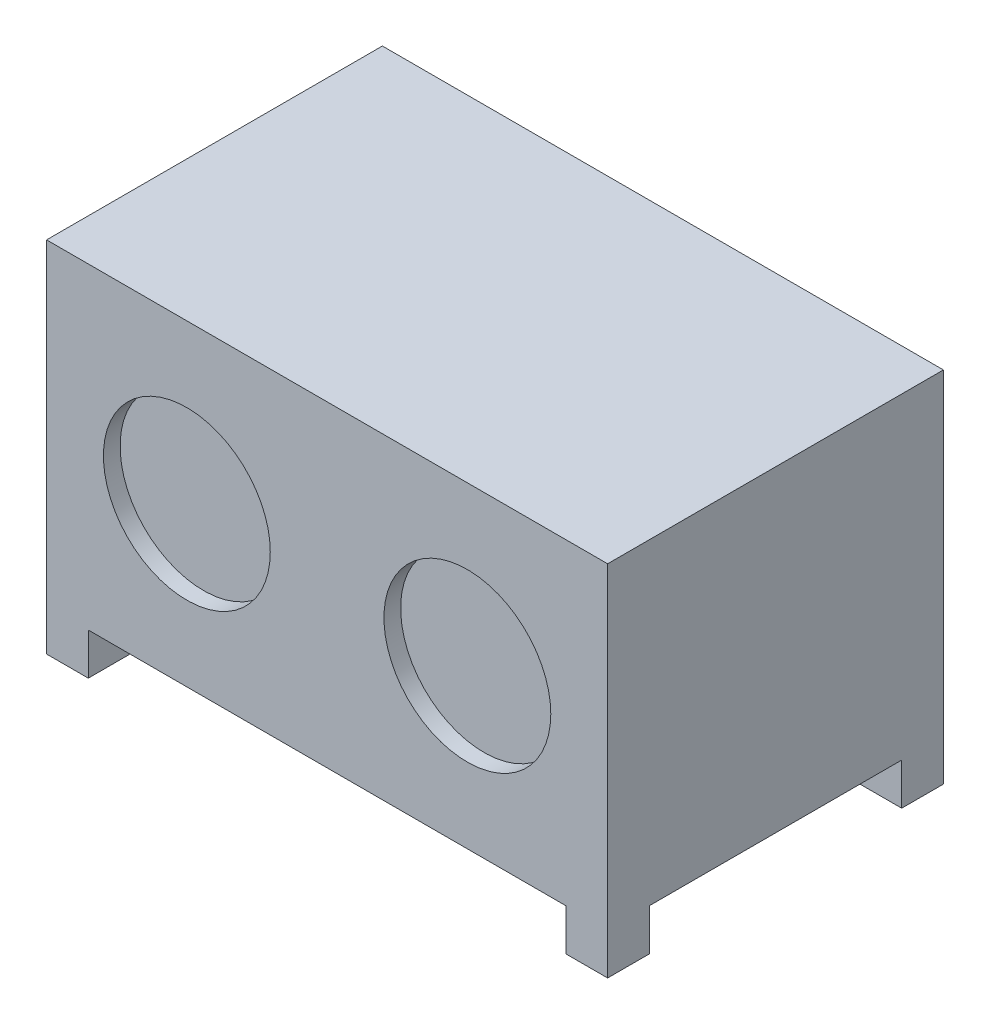
SolidWorks part; units mm, degrees
ref_plane "Front" through (0, 0, 0) normal (0, 0, 1) x (1, 0, 0)
ref_plane "Top" through (0, 0, 0) normal (0, 1, 0) x (1, 0, 0)
ref_plane "Right" through (0, 0, 0) normal (1, 0, 0) x (0, 0, -1)
sketch "Sketch1" plane through (0, 0, 0) normal (0, 1, 0) x (1, 0, 0)
  line L1 (-854.075, 511.175) -> (854.075, 511.175)
  line L2 (-854.075, 511.175) -> (-854.075, -511.175)
  line L3 (-854.075, -511.175) -> (854.075, -511.175)
  line L4 (854.075, 511.175) -> (854.075, -511.175)
  line L5 (-854.075, 511.175) -> (854.075, -511.175) construction
  line L6 (-854.075, -511.175) -> (854.075, 511.175) construction
  point P0 (0, 0)
  dimension "D1" = 1708.15
  dimension "D2" = 1022.35
extrude "Boss-Extrude1" add sketch "Sketch1" along normal blind 965.2
sketch "Sketch2" plane through (0, 0, 511.175) normal (0, 0, 1) x (1, 0, 0)
  line L0 (0, 0) -> (0, 965.2) construction
  line L1 (-854.075, 0) -> (854.075, 0) construction
  line L2 (-854.075, 965.2) -> (854.075, 965.2) construction
  line L3 (0, 482.6) -> (-854.075, 482.6) construction
  line L4 (-854.075, 965.2) -> (-854.075, 0) construction
  line L5 (0, 482.6) -> (854.075, 482.6) construction
  line L6 (854.075, 965.2) -> (854.075, 0) construction
  circle A0 centre (427.0375, 482.6) radius 254
  circle A1 centre (-427.0375, 482.6) radius 254
  dimension "D1" = 508
extrude "Cut-Extrude1" cut sketch "Sketch2" against normal blind 50.8
sketch "Sketch3" plane through (0, 0, 0) normal (0, -1, 0) x (1, 0, 0)
  line L1 (-854.075, 511.175) -> (-727.075, 511.175)
  line L2 (-854.075, 511.175) -> (-854.075, 384.175)
  line L3 (-854.075, 384.175) -> (-727.075, 384.175)
  line L4 (-727.075, 511.175) -> (-727.075, 384.175)
  line L5 (-854.075, -511.175) -> (-727.075, -511.175)
  line L6 (-854.075, -511.175) -> (-854.075, -384.175)
  line L7 (-854.075, -384.175) -> (-727.075, -384.175)
  line L8 (-727.075, -511.175) -> (-727.075, -384.175)
  line L9 (854.075, 511.175) -> (727.075, 511.175)
  line L10 (854.075, 511.175) -> (854.075, 384.175)
  line L11 (854.075, 384.175) -> (727.075, 384.175)
  line L12 (727.075, 511.175) -> (727.075, 384.175)
  line L13 (854.075, -511.175) -> (727.075, -511.175)
  line L14 (854.075, -511.175) -> (854.075, -384.175)
  line L15 (854.075, -384.175) -> (727.075, -384.175)
  line L16 (727.075, -511.175) -> (727.075, -384.175)
  dimension "D1" = 127
extrude "Boss-Extrude2" add sketch "Sketch3" along normal blind 127
